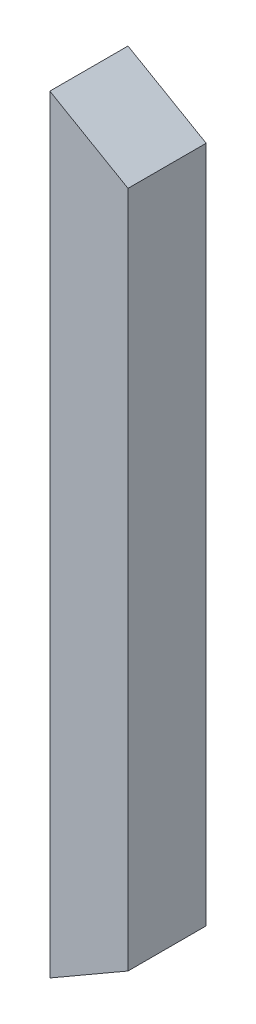
SolidWorks part; units mm, degrees
ref_plane "Plan de face" through (0, 0, 0) normal (0, 0, 1) x (1, 0, 0)
ref_plane "Plan de dessus" through (0, 0, 0) normal (0, 1, 0) x (1, 0, 0)
ref_plane "Plan de droite" through (0, 0, 0) normal (1, 0, 0) x (0, 0, -1)
sketch "Esquisse1" plane through (0, 0, 0) normal (0, 0, 1) x (1, 0, 0)
  line L1 (0, 0) -> (60, 0)
  line L2 (0, 0) -> (0, 555)
  line L3 (0, 555) -> (60, 555)
  line L4 (60, 0) -> (60, 555)
  dimension "D1" = 555
  dimension "D2" = 60
extrude "Boss.-Extru.1" add sketch "Esquisse1" along normal blind 60
sketch "Esquisse2" plane through (0, 0, 60) normal (0, 0, 1) x (1, 0, 0)
  line L0 (60, 0) -> (0, 0)
  line L1 (0, 0) -> (0, -34.641)
  line L2 (0, -34.641) -> (60, 0)
  dimension "D1" = 30
extrude "Boss.-Extru.2" add sketch "Esquisse2" against normal up to vertex (60 mm away) up to point (60, 0, 0)
sketch "Esquisse3" plane through (0, 0, 60) normal (0, 0, 1) x (1, 0, 0)
  line L0 (60, 520.359) -> (0, 555)
  line L1 (60, 0) -> (60, 555) construction
  line L2 (0, 555) -> (60, 555)
  line L3 (60, 555) -> (60, 520.359)
  dimension "D1" = 30
extrude "Enlèv. mat.-Extru.1" cut sketch "Esquisse3" against normal through all both and the other way through all
